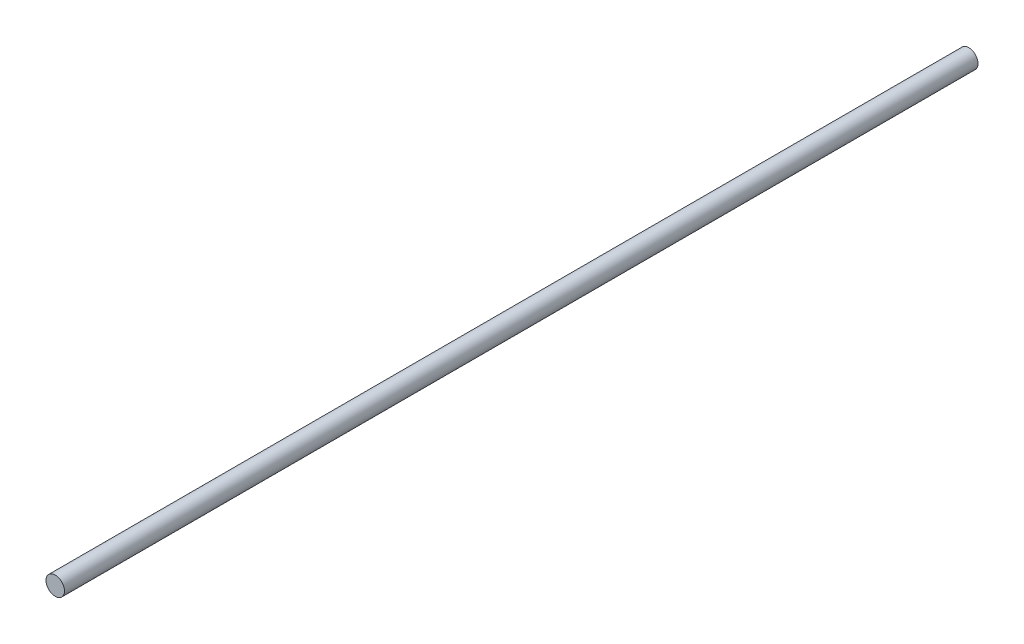
SolidWorks part; units mm, degrees
material "AISI 316 Stainless Steel Sheet (SS)"
ref_plane "Front (1)" through (0, 0, 0) normal (0, 0, 1) x (1, 0, 0)
ref_plane "Top (2)" through (0, 0, 0) normal (0, 1, 0) x (1, 0, 0)
ref_plane "Right (3)" through (0, 0, 0) normal (1, 0, 0) x (0, 0, -1)
ref_axis "X Axis" through (13.5064, 0, 0) along (-1, 0, 0)
ref_axis "Y Axis" through (0, 12.3593, 0) along (0, -1, 0)
ref_axis "Z Axis" through (0, 0, 14.1119) along (0, 0, -1)
sketch "Sketch2" plane through (0, 0, 0) normal (1, 0, 0) x (0, 0, -1)
  line L0 (-7.8, 0) -> (0, 0) construction
  line L1 (-7.8, 0) -> (387.5532, 0)
  line L2 (-7.8, 0) -> (-7.8, 4)
  line L3 (-7.8, 4) -> (387.5532, 4)
  line L4 (387.5532, 0) -> (387.5532, 4)
  point P4 (0, 0)
  dimension "D1" = 395.3532
revolve "Revolve1" add sketch "Sketch2" angle 360 about L0
